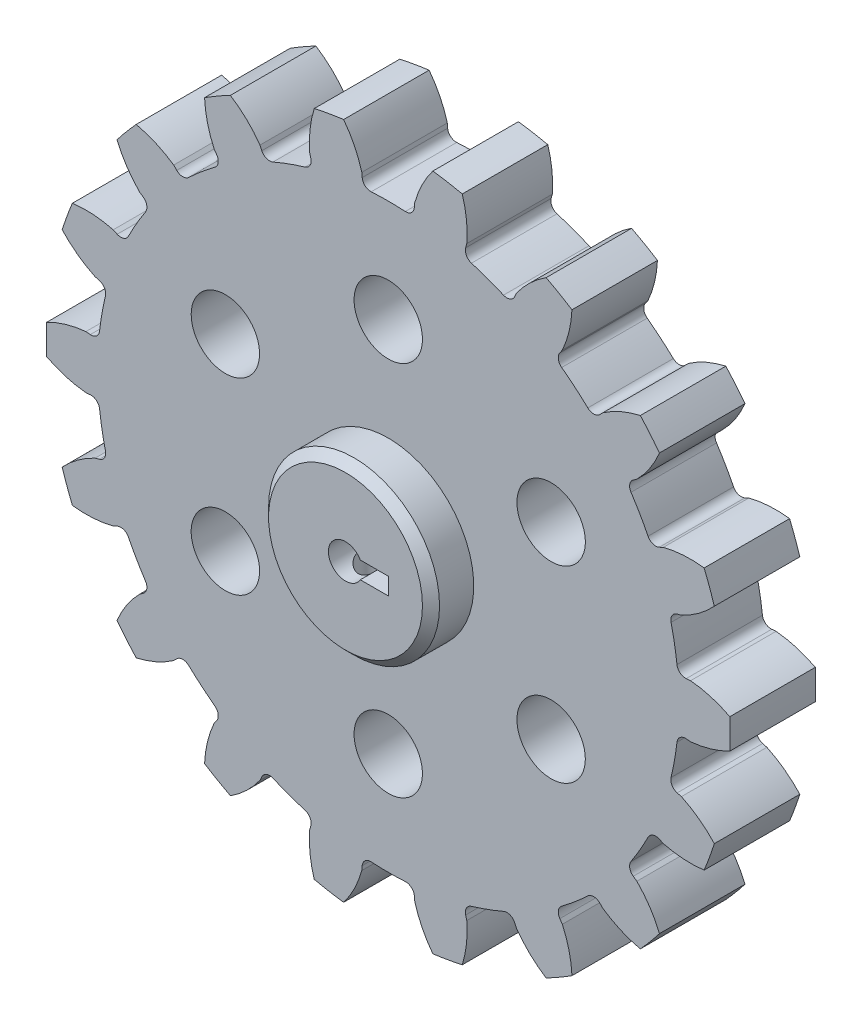
SolidWorks part; units mm, degrees
ref_plane "Plan de face" through (0, 0, 0) normal (0, 0, 1) x (1, 0, 0)
ref_plane "Plan de dessus" through (0, 0, 0) normal (0, 1, 0) x (1, 0, 0)
ref_plane "Plan de droite" through (0, 0, 0) normal (1, 0, 0) x (0, 0, -1)
sketch "Esquisse1" plane through (0, 0, 0) normal (0, 0, 1) x (1, 0, 0)
  line L0 (0, 0) -> (49.1646, 0) construction
  line L1 (0, 0) -> (33.4835, 5.904) construction
  line L2 (0, 0) -> (40.5362, 3.5465) construction
  line L3 (0, 0) -> (40.5296, 1.7696) construction
  line L4 (33.8706, -2.9633) -> (35.3649, -3.094)
  line L5 (0, 0) -> (33.4835, 5.904)
  line L6 (33.8706, 2.9633) -> (35.3649, 3.094)
  line L7 (0, 0) -> (33.4835, -5.904)
  circle A0 centre (0, 0) radius 40 construction
  circle A1 centre (0, 0) radius 35.5 construction
  circle A2 centre (0, 0) radius 34 construction
  arc A3 (33.4835, 5.904) -> (33.8706, 2.9633) centre (0, 0) cw
  arc A4 (39.9546, -1.7445) -> (39.9546, 1.7445) centre (0, 0) ccw
  arc A5 (35.3649, 3.094) -> (39.9546, 1.7445) centre (34.1869, -9.3916) cw
  arc A6 (35.3649, -3.094) -> (39.9546, -1.7445) centre (34.1869, 9.3916) ccw
  arc A7 (33.4835, -5.904) -> (33.8706, -2.9633) centre (0, 0) ccw
  dimension "D1" = 80
  dimension "D2" = 71
  dimension "D3" = 6
  dimension "D4" = 10
  dimension "D5" = 5
  dimension "D6" = 2.5
extrude "Boss.-Extru.1" add sketch "Esquisse1" along normal blind 10 contours L7 A7 L4 A6 A4 A5 L6 A3 L5
fillet "Congé1" radius 1 2 edges at (33.8706, -2.9633, 5) (33.8706, 2.9633, 5)
pattern_circular "Répétition circulaire2" count 18 over 360 about axis through (0, 0, 10) along (0, 0, -1) of "Congé1", "Boss.-Extru.1" reverse direction yes
sketch "Esquisse3" plane through (0, 0, 10) normal (0, 0, 1) x (1, 0, 0)
  circle A0 centre (0, 0) radius 10
  dimension "D1" = 20
extrude "Boss.-Extru.2" add sketch "Esquisse3" along normal blind 5
sketch "Esquisse5" plane through (0, 0, 15) normal (0, 0, 1) x (1, 0, 0)
  circle A0 centre (0, 0) radius 2
  dimension "D1" = 4
sketch "Esquisse7" plane through (0, 0, 15) normal (0, 0, 1) x (1, 0, 0)
  line L1 (0, 1) -> (5, 1)
  line L2 (0, 1) -> (0, -1)
  line L3 (0, -1) -> (5, -1)
  line L4 (5, 1) -> (5, -1)
  dimension "D1" = 1
  dimension "D2" = 1
  dimension "D3" = 5
extrude "Enlèv. mat.-Extru.2" cut sketch "Esquisse7" against normal up to surface (5 mm away) contours L1 L4 L3 L2 up to face at (-10, 0, 10)
extrude "Enlèv. mat.-Extru.3" cut sketch "Esquisse5" against normal up to surface (15 mm away) up to face at (0, 0, 0)
sketch "Esquisse8" plane through (0, 0, 0) normal (0, 1, 0) x (1, 0, 0)
  line L0 (-10, -15) -> (10, -15) construction
  circle A0 centre (0, -12) radius 1.5
  dimension "D1" = 3
  dimension "D2" = 3
extrude "Enlèv. mat.-Extru.4" cut sketch "Esquisse8" against normal up to surface (10 mm away) contours A0 up to face at (10, 0, 15)
chamfer "Chanfrein1" distance 1 angle 45 1 edges at (10, 0, 15)
sketch "Esquisse9" plane through (0, 0, 10) normal (0, 0, 1) x (1, 0, 0)
  circle A0 centre (0, 22) radius 4
  dimension "D1" = 8
  dimension "D2" = 22
extrude "Enlèv. mat.-Extru.5" cut sketch "Esquisse9" against normal up to surface (10 mm away) up to face at (-2, 0, 0)
pattern_circular "Répétition circulaire3" count 6 over 360 about axis through (0, 0, 15) along (0, 0, -1) of "Enlèv. mat.-Extru.5"
